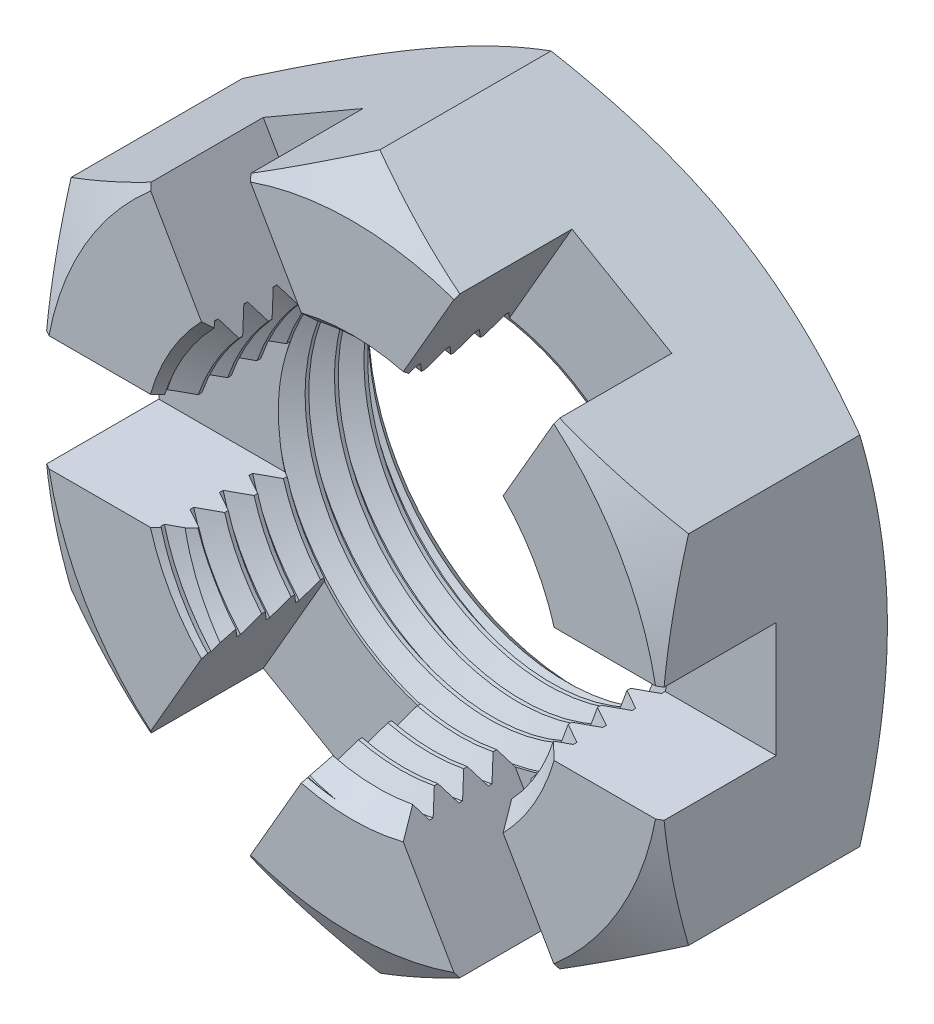
SolidWorks part; units mm, degrees
material "AISI 4340 Steel, annealed"
ref_plane "Front Plane" through (0, 0, 0) normal (0, 0, 1) x (1, 0, 0)
ref_plane "Top Plane" through (0, 0, 0) normal (0, 1, 0) x (1, 0, 0)
ref_plane "Right Plane" through (0, 0, 0) normal (1, 0, 0) x (0, 0, -1)
sketch "Sketch1" plane through (0, 0, 0) normal (0, 0, 1) x (1, 0, 0)
  line L1 (0, 21.997) -> (-19.05, 10.9985)
  line L2 (-19.05, 10.9985) -> (-19.05, -10.9985)
  line L3 (-19.05, -10.9985) -> (0, -21.997)
  line L4 (0, -21.997) -> (19.05, -10.9985)
  line L5 (19.05, -10.9985) -> (19.05, 10.9985)
  line L6 (19.05, 10.9985) -> (0, 21.997)
  circle A0 centre (0, 0) radius 19.05 construction
  dimension "Hex" = 38.1
extrude "Extrude1" add sketch "Sketch1" against normal blind 13.97
sketch "Sketch2" plane through (0, 0, 0) normal (0, 0, 1) x (1, 0, 0)
  circle A0 centre (0, 0) radius 19.05 construction
  circle A1 centre (0, 0) radius 19.05
extrude "Cut-Extrude1" cut sketch "Sketch2" against normal through all draft 60 flip side to cut
sketch "Sketch3" plane through (0, 0, -13.97) normal (0, 0, -1) x (-1, 0, 0)
  circle A1 centre (0, 0) radius 19.05
  circle A2 centre (0, 0) radius 19.05
  dimension "D1" = 0
extrude "Cut-Extrude2" cut sketch "Sketch3" against normal through all draft 60 flip side to cut
sketch "Sketch4" plane through (0, 0, 0) normal (0, 0, 1) x (1, 0, 0)
  circle A0 centre (0, 0) radius 12.7
  dimension "Thread Dia" = 25.4
extrude "Cut-Extrude3" cut sketch "Sketch4" against normal through all
sketch "Sketch7" plane through (0, 0, 0) normal (0, 0, 1) x (1, 0, 0)
  circle A4 centre (0, 0) radius 12.954
  circle A5 centre (0, 0) radius 12.954
  dimension "D1" = 0.254
sketch "Sketch8" plane through (0, 0, -13.97) normal (0, 0, -1) x (-1, 0, 0)
  circle A1 centre (0, 0) radius 12.954
  circle A2 centre (0, 0) radius 12.954 construction
sketch "Sketch5" plane through (0, 0, 0) normal (0, 0, 1) x (1, 0, 0)
  circle A0 centre (0, 0) radius 12.7 construction
  circle A1 centre (0, 0) radius 12.7
curve "Helix/Spiral1" pitch 1.8143 height 15.7843 turns 8.7 parameters "pitch"=1.8143
sketch "Sketch9" plane through (0, 0, 0) normal (1, 0, 0) x (0, 0, -1)
  line L0 (-0.9071, 12.7) -> (-0.6804, 12.7)
  line L1 (-0.6804, 12.7) -> (0, 11.5216)
  line L2 (-0.9071, 12.7) -> (-1.5875, 11.5216)
  line L3 (-1.5875, 11.5216) -> (0, 11.5216)
  line L4 (-0.7937, 12.7) -> (-0.7937, 11.5216) construction
  line L5 (-1.2473, 12.1108) -> (-0.3402, 12.1108) construction
  line L7 (0, 11.5216) -> (0, 12.7) construction
  line L8 (0, 12.7) -> (0, -12.7) construction
  dimension "D1" = 0.2268
  dimension "D2" = 0.9071
  dimension "D3" = 60
sketch "Sketch12" plane through (0, 0, 0) normal (0, 0, 1) x (1, 0, 0)
  circle A0 centre (0, 0) radius 11.5216
  circle A1 centre (0, 0) radius 12.7 construction
  circle A2 centre (0, 0) radius 12.7
extrude "Extrude2" add sketch "Sketch12" against normal up to surface (13.97 mm away) up to face at (12.7, 0, -13.97)
sweep "Cut-Sweep1" cut profiles "Sketch9" path "Helix/Spiral1"
extrude "Cut-Extrude6" cut sketch "Sketch7" against normal through all draft 45
extrude "Cut-Extrude7" cut sketch "Sketch8" against normal through all draft 45
sketch "Sketch13" plane through (0, 0, 0) normal (0, 0, 1) x (1, 0, 0)
  line L0 (-3.0796, 1.778) -> (3.0796, -1.778)
  line L1 (-3.0796, 1.778) -> (6.4454, 18.2758)
  line L2 (3.0796, -1.778) -> (12.6046, 14.7198)
  line L3 (6.4454, 18.2758) -> (12.6046, 14.7198)
  line L4 (19.05, 10.9985) -> (9.525, 16.4978) construction
  dimension "slot width" = 7.112
extrude "Cut-Extrude8" cut sketch "Sketch13" against normal blind 7.112
pattern_circular "CirPattern1" count 6 over 360 about axis through (0, 0, 0) along (0, 0, 1) of "Cut-Extrude8"
equation "\"D2@Sketch9\" = \"pitch@Helix/Spiral1\"*.5"
equation "\"D3@Helix/Spiral1\" = \"pitch@Helix/Spiral1\"+\"Height@Extrude1\""
equation "\"D1@Sketch9\" = \"pitch@Helix/Spiral1\"*.125"
